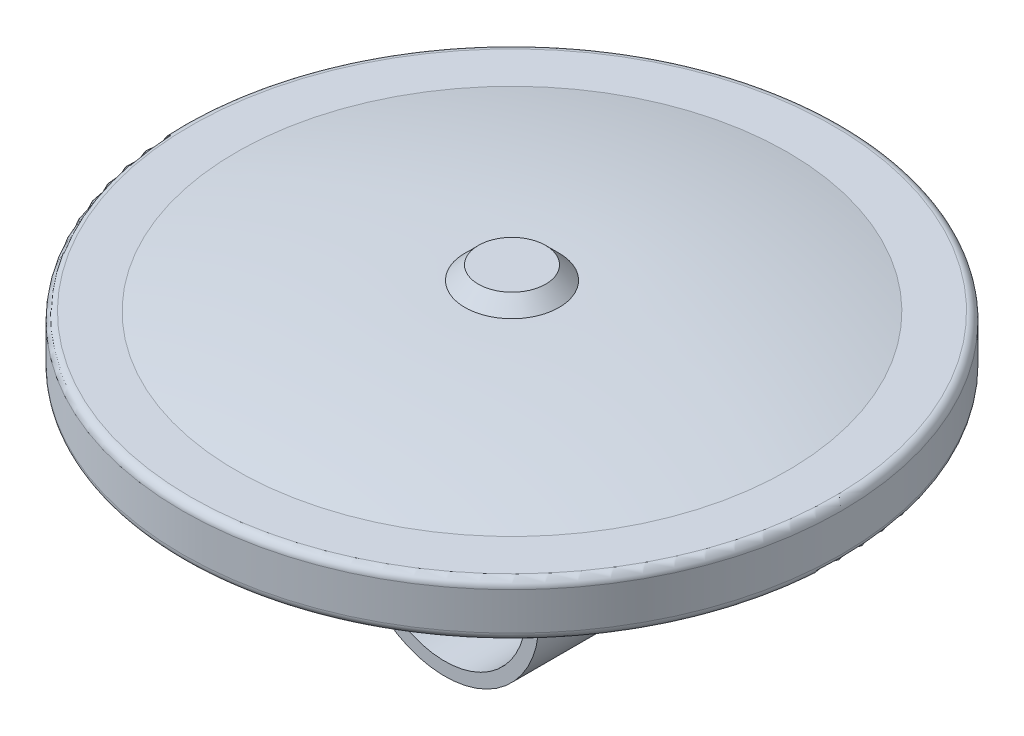
SolidWorks part; units mm, degrees
ref_plane "Front Plane" through (0, 0, 0) normal (0, 0, 1) x (1, 0, 0)
ref_plane "Top Plane" through (0, 0, 0) normal (0, 1, 0) x (1, 0, 0)
ref_plane "Right Plane" through (0, 0, 0) normal (1, 0, 0) x (0, 0, -1)
sketch "Sketch1" plane through (0, 0, 0) normal (0, 0, 1) x (1, 0, 0)
  line L0 (0, 0) -> (0, 50) construction
  line L1 (11, 0) -> (11, 30)
  line L2 (11, 30) -> (103.8397, 30)
  line L3 (103.8397, 30) -> (112.5, 15)
  line L4 (112.5, 15) -> (122.5, 15)
  line L5 (122.5, 15) -> (122.5, 35)
  line L6 (122.5, 35) -> (102.5, 35)
  line L7 (0, 50) -> (12.5, 50)
  line L8 (12.5, 50) -> (17.5, 45)
  line L9 (17.5, 45) -> (0, 45) construction
  line L10 (11, 0) -> (8, 0)
  line L11 (8, 0) -> (8, 40)
  line L12 (8, 40) -> (0, 40)
  line L13 (0, 50) -> (0, 40)
  arc A0 (17.5, 45) -> (102.5, 35) centre (17.5, -321.25) cw
  point P13 (6.25, 50)
  dimension "D1" = 245
  dimension "D2" = 16
  dimension "D3" = 22
  dimension "D4" = 50
  dimension "D5" = 25
  dimension "D6" = 5
  dimension "D7" = 20
  dimension "D8" = 20
  dimension "D9" = 45
  dimension "D10" = 10
  dimension "D11" = 30
  dimension "D12" = 15
  dimension "D13" = 30
  dimension "D14" = 10
revolve "Revolve1" add sketch "Sketch1" angle 360 about L0
fillet "Fillet1" radius 3 2 edges at (0, 15, -122.5) (0, 35, -122.5)
thread "Thread1" pitch 2 method cut profile "Thread Profile1" start angle 0, offset 2, length 10, pitch 2, diameter 22
ref_plane "Plane1" through (11, -2, 0) normal (0, 0, 1) x (1, 0, 0)
sketch "Thread Profile1" plane through (11, -2, 0) normal (0, 0, 1) x (1, 0, 0)
  line L0 (0, 0) -> (0, 2) construction
  line L11 (0, 0) -> (0, 1.75)
  line L12 (0, 1.75) -> (-1.0825, 1.125)
  line L13 (-1.0825, 1.125) -> (-1.0825, 0.625)
  line L15 (-1.0825, 0.625) -> (0, 0)
  line L17 (-1.0825, 0.875) -> (0, 0.875) construction
  point P2 (0, 0)
  dimension "Pitch" = 2
  dimension "Profile_Angle" = 60
  dimension "Profile_Land" = 0.5
  dimension "Profile_Height" = 1.0825
sketch "Sketch2" plane through (0, 0, 0) normal (0, -1, 0) x (1, 0, 0)
  circle A0 centre (0, 0) radius 9.5
  circle A1 centre (0, 0) radius 15
  dimension "D1" = 19
  dimension "D2" = 30
sketch "Sketch3" plane through (0, 0, 0) normal (0, 0, 1) x (1, 0, 0)
  line L0 (0, 0) -> (0, -35) construction
  circle A0 centre (0, -35) radius 35
  circle A1 centre (0, -35) radius 30.15
  dimension "D1" = 70
  dimension "D2" = 60.3
extrude "Boss-Extrude1" add sketch "Sketch3" along normal mid plane 50 separate body
extrude "Boss-Extrude3" add sketch "Sketch2" along normal up to surface and the other way blind 15 separate body up to face at (35, -35, 25)
other "CPoint1" parameters "Diameter"=50.8, "StubLength"=228.6
ref_axis "Axis1" through (0, -35, 35) along (0, 0, -1)
other "CPoint2" parameters "Diameter"=50.8, "StubLength"=228.6
ref_axis "Axis2" through (0, -35, -35) along (0, 0, 1)
other "RPoint1"
ref_axis "Vertical" through (0, 0, 0) along (0, -1, 0)
